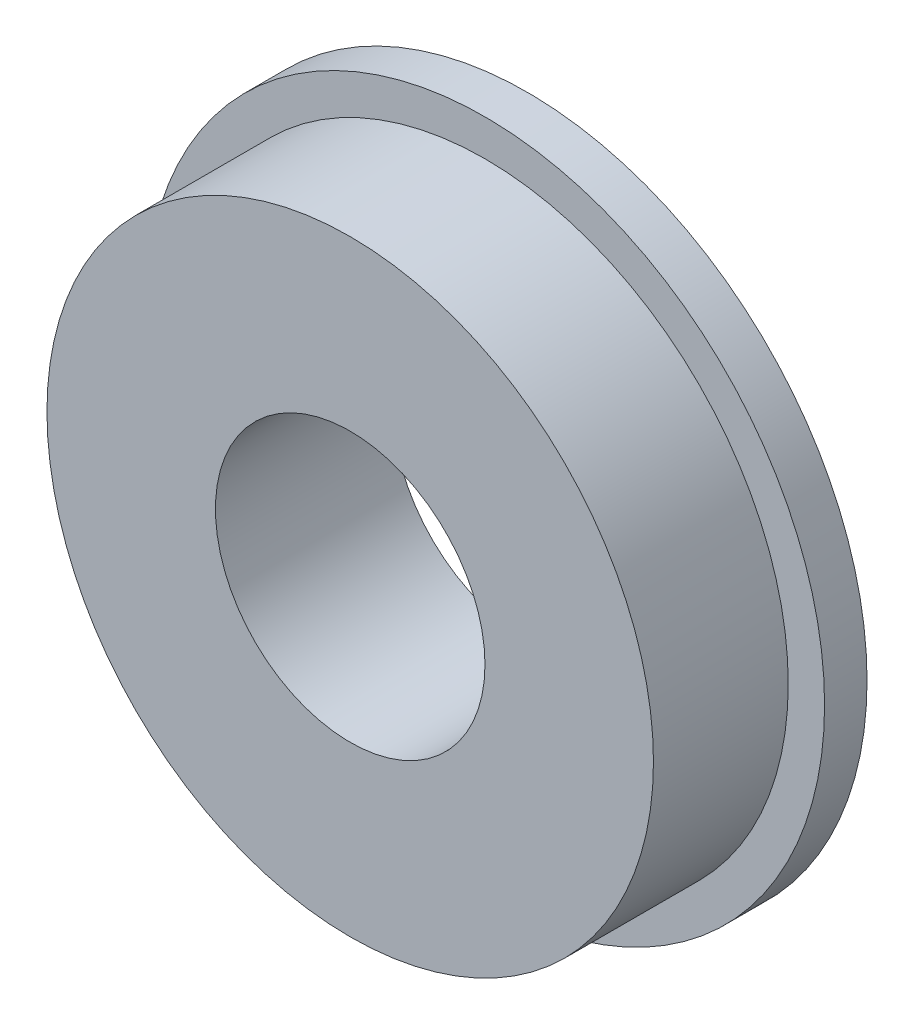
SolidWorks part; units mm, degrees
ref_plane "Front Plane" through (0, 0, 0) normal (0, 0, 1) x (1, 0, 0)
ref_plane "Top Plane" through (0, 0, 0) normal (0, 1, 0) x (1, 0, 0)
ref_plane "Right Plane" through (0, 0, 0) normal (1, 0, 0) x (0, 0, -1)
sketch "Sketch1" plane through (0, 0, 0) normal (0, 0, 1) x (1, 0, 0)
  circle A0 centre (0, 0) radius 16
  dimension "D1" = 32
extrude "Boss-Extrude1" add sketch "Sketch1" along normal blind 2
sketch "Sketch2" plane through (0, 0, 2) normal (0, 0, 1) x (1, 0, 0)
  circle A0 centre (0, 0) radius 14.2875
  dimension "D1" = 28.575
extrude "Boss-Extrude2" add sketch "Sketch2" along normal blind 6.35
sketch "Sketch3" plane through (0, 0, 8.35) normal (0, 0, 1) x (1, 0, 0)
  circle A0 centre (0, 0) radius 6.35
  dimension "D1" = 12.7
extrude "Cut-Extrude1" cut sketch "Sketch3" against normal up to surface (8.35 mm away) up to face at (16, 0, 0)
